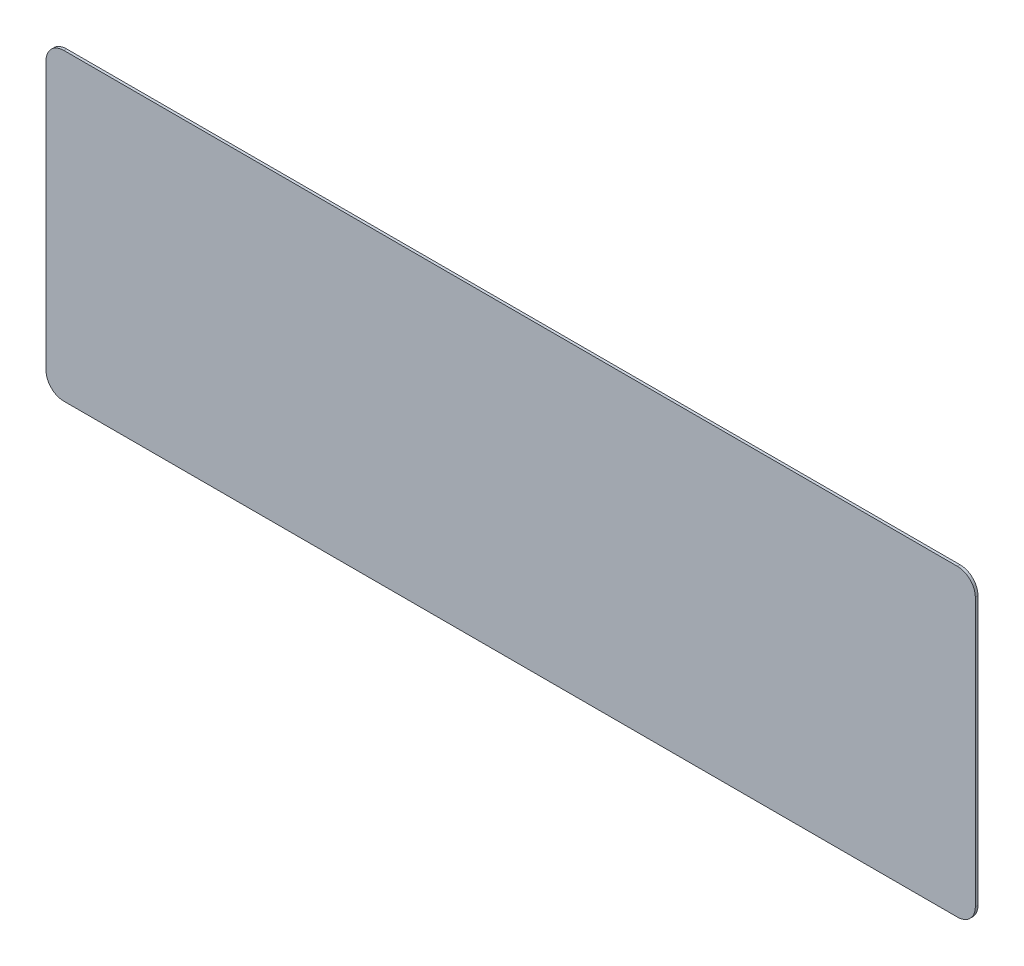
SolidWorks part; units mm, degrees
material "1.0037 (S235JR)"
ref_plane "Front Plane" through (0, 0, 0) normal (0, 0, 1) x (1, 0, 0)
ref_plane "Top Plane" through (0, 0, 0) normal (0, 1, 0) x (1, 0, 0)
ref_plane "Right Plane" through (0, 0, 0) normal (1, 0, 0) x (0, 0, -1)
sketch "Sketch1" plane through (0, 0, 0) normal (0, 0, 1) x (1, 0, 0)
  line L1 (260, -85) -> (-260, -85)
  line L2 (260, -85) -> (260, 85)
  line L3 (260, 85) -> (-260, 85)
  line L4 (-260, -85) -> (-260, 85)
  line L5 (260, -85) -> (-260, 85) construction
  line L6 (260, 85) -> (-260, -85) construction
  point P0 (0, 0)
  dimension "D1" = 520
  dimension "D2" = 170
base flange "Base-Flange1" sketch "Sketch1" thickness 1.5 reverse thickness direction no parameters "D1"=0.7366
fillet "Fillet1" radius 10 4 edges at (260, -85, -0.75) (260, 85, -0.75) (-260, 85, -0.75) (-260, -85, -0.75)
sketch "Bend-Lines1" [suppressed] plane through (0, 0, 0) normal (0, 1, 0) x (1, 0, 0)
sketch "Bounding-Box1" [suppressed] plane through (0, 0, 0) normal (0, 1, 0) x (1, 0, 0)
sheet metal parameters "Sheet-Metal1" thickness 1.5 parameters "D1"=0.7366
flat pattern "Flat-Pattern1" [suppressed]
sketch "Bend-Lines2" plane through (0, 0, 0) normal (0, 1, 0) x (1, 0, 0)
sketch3d "Bounding-Box2" [suppressed]
  line L0 (-260, -85, 0) -> (260, -85, 0) construction
  line L1 (-260, 85, 0) -> (260, 85, 0) construction
  line L2 (-260, -85, 0) -> (-260, 85, 0) construction
  line L3 (260, -85, 0) -> (260, 85, 0) construction
